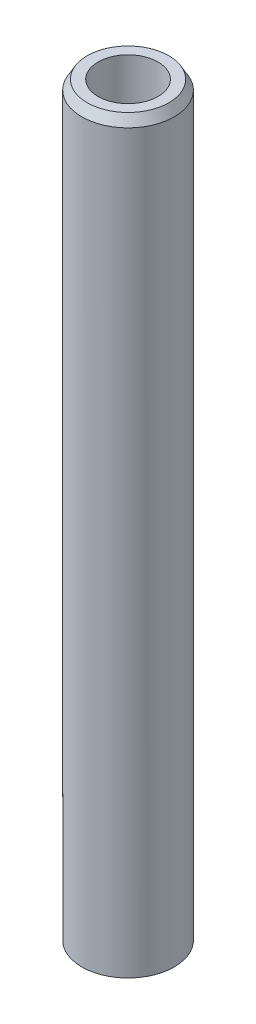
SolidWorks part; units mm, degrees
ref_plane "Front Plane" through (0, 0, 0) normal (0, 0, 1) x (1, 0, 0)
ref_plane "Top Plane" through (0, 0, 0) normal (0, 1, 0) x (1, 0, 0)
ref_plane "Right Plane" through (0, 0, 0) normal (1, 0, 0) x (0, 0, -1)
sketch "Sketch1" plane through (0, 0, 0) normal (0, 1, 0) x (1, 0, 0)
  circle A0 centre (0, 0) radius 15
  dimension "SHAFT_OD" = 30
extrude "Boss-Extrude1" add sketch "Sketch1" along normal blind 243.7272
sketch "Sketch2" plane through (0, 0, 0) normal (0, 1, 0) x (1, 0, 0)
  circle A0 centre (0, 0) radius 9.7222
  dimension "BORE_D" = 19.4444
extrude "Cut-Extrude1" cut sketch "Sketch2" along normal through all
chamfer "Chamfer1" distance 3.07 angle 30 2 edges at (0, 243.7272, 15) (0, 0, 15) first distance on face at (0, 243.7272, 15) first distance on face at (0, 0, 9.7222)
